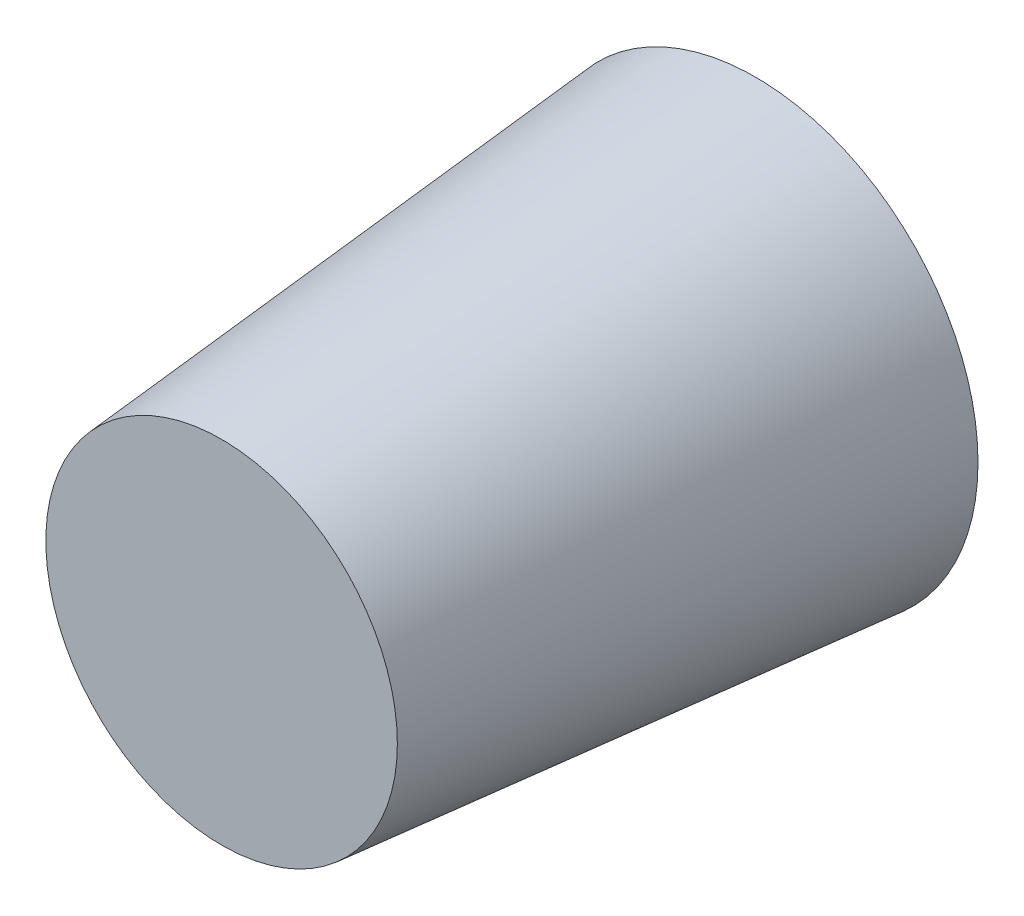
SolidWorks part; units mm, degrees
ref_plane "Alzado" through (0, 0, 0) normal (0, 0, 1) x (1, 0, 0)
ref_plane "Planta" through (0, 0, 0) normal (0, 1, 0) x (1, 0, 0)
ref_plane "Vista lateral" through (0, 0, 0) normal (1, 0, 0) x (0, 0, -1)
sketch "Croquis2" plane through (0, 0, 0) normal (0, 0, 1) x (1, 0, 0)
  circle A0 centre (75, 144) radius 1.5
  circle A2 centre (75, 144) radius 2.5
extrude "Saliente-Extruir1" add sketch "Croquis2" along normal blind 6 draft 5 contours A2 A0 | A0 region at (75, 144, 0) region at (72.5707, 144, 0)
extrude "Cortar-Extruir1" cut sketch "Croquis2<3>" along normal blind 5.5 draft 5 contours A0 region at (75, 144, 0)
sketch "Croquis2<3>" plane through (0, 0, 0) normal (0, 0, 1) x (1, 0, 0) same geometry as "Croquis2"
